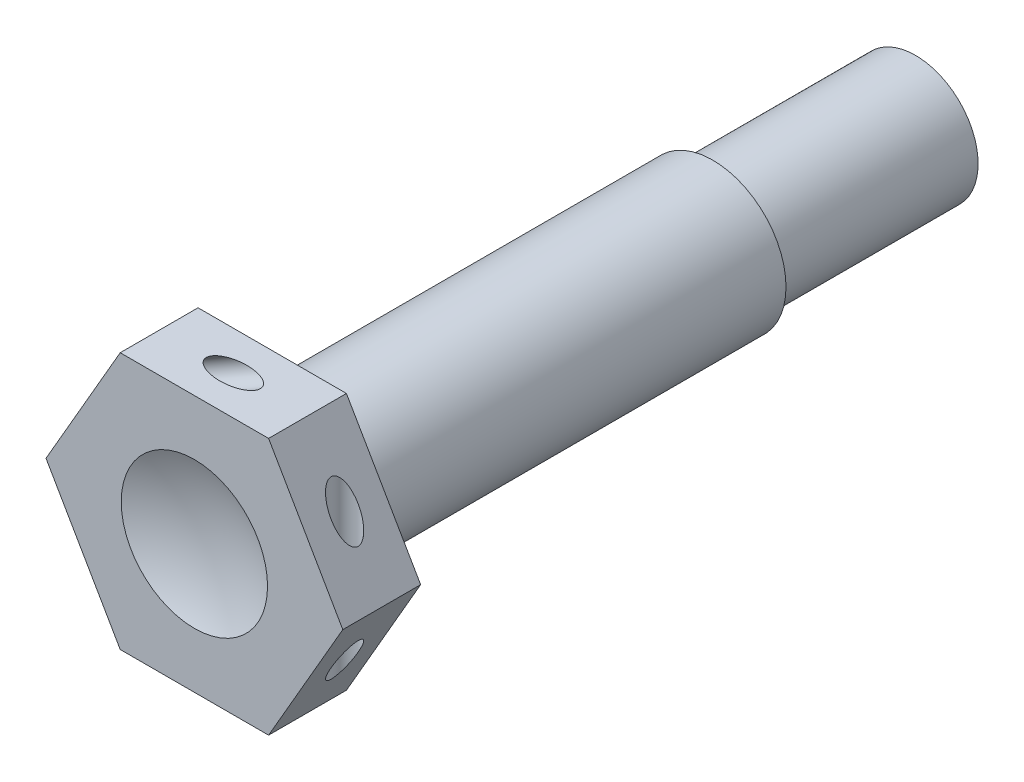
SolidWorks part; units mm, degrees
material "Alloy Steel"
ref_plane "Plane1" through (0, 0, 0) normal (0, 0, 1) x (1, 0, 0)
ref_plane "Plane2" through (0, 0, 0) normal (0, 1, 0) x (1, 0, 0)
ref_plane "Plane3" through (0, 0, 0) normal (1, 0, 0) x (0, 0, -1)
ref_axis "Axis1" through (-83.9706, 0, 0) along (1, 0, 0)
ref_axis "Axis2" through (0, 0, -29.3719) along (0, 0, 1)
ref_axis "Axis3" through (0, 6.1119, 0) along (0, -1, 0)
sketch "Sketch1" plane through (0, 0, 0) normal (0, 0, 1) x (1, 0, 0)
  line L1 (3.2079, 5.5562) -> (-3.2079, 5.5562)
  line L2 (-3.2079, 5.5562) -> (-6.4158, 0)
  line L3 (-6.4158, 0) -> (-3.2079, -5.5563)
  line L4 (-3.2079, -5.5563) -> (3.2079, -5.5563)
  line L5 (3.2079, -5.5563) -> (6.4158, 0)
  line L6 (6.4158, 0) -> (3.2079, 5.5562)
  circle A0 centre (0, 0) radius 5.5562 construction
  dimension "D1" = 11.1125
extrude "Boss-Extrude1" add sketch "Sketch1" along normal blind 3.3655
sketch "Sketch2" plane through (0, 0, 0) normal (0, 0, -1) x (-1, 0, 0)
  circle A0 centre (0, 0) radius 3.1623
  dimension "D1" = 6.3246
extrude "Boss-Extrude2" add sketch "Sketch2" along normal blind 19.05
sketch "Sketch3" plane through (0, 0, -19.05) normal (0, 0, -1) x (-1, 0, 0)
  circle A0 centre (0, 0) radius 2.7051
  dimension "D1" = 5.4102
extrude "Boss-Extrude3" add sketch "Sketch3" along normal blind 8.763
sketch "Sketch4" plane through (0, 0, 0) normal (1, 0, 0) x (0, 0, -1)
  line L0 (-3.3655, 0) -> (-3.3655, 3.1623)
  line L1 (-3.3655, 0) -> (-3.3655, 5.5562) construction
  line L2 (-3.3655, 0) -> (0, 0) construction
  line L3 (-3.3655, 0) -> (-2.6644, 0)
  line L4 (-2.6644, 0) -> (-2.6644, 2.4426) construction
  line L5 (-3.3655, 3.1623) -> (-3.5111, 3.4745) construction
  arc A0 (-3.3655, 3.1623) -> (-2.6644, 0) centre (-10.1471, 0) cw
  dimension "D1" = 3.1623
  dimension "D2" = 25
revolve "Cut-Revolve1" cut sketch "Sketch4" angle 360 about L3
sketch "Sketch5" plane through (0, 0, 0) normal (0, 1, 0) x (1, 0, 0)
  line L0 (4.8119, -1.6827) -> (6.4158, -1.6827) construction
  line L1 (6.4158, -3.3655) -> (6.4158, 0) construction
  line L2 (4.8119, -1.6827) -> (3.2079, -1.6827) construction
  line L4 (3.2079, -3.3655) -> (3.2079, 0) construction
  circle A0 centre (4.8119, -1.6827) radius 0.5842
  dimension "D1" = 1.1684
extrude "Cut-Extrude1" cut sketch "Sketch5" against normal through all and the other way through all
pattern_circular "CirPattern1" count 3 over 360 about axis through (0, 0, -29.3719) along (0, 0, 1) of "Cut-Extrude1"
equation "\"hexwid\"= 0.4375"
equation "\"hexht\"= 0.1325"
equation "\"gripd\"= 0.249"
equation "\"threadd\"= 0.213"
equation "\"threadlen\"= 0.37"
equation "\"wd\"= 0.046"
equation "\"griplen\"= 0.75"
equation "\"D1@Sketch1\" = \"hexwid\""
equation "\"D1@Boss-Extrude1\" = \"hexht\""
equation "\"D1@Sketch2\" = \"gripd\""
equation "\"D1@Boss-Extrude2\" = \"griplen\""
equation "\"D1@Sketch3\" = \"threadd\""
equation "\"D1@Sketch4\" = \"gripd\"/2"
equation "\"D2@Sketch4\" = 25deg"
equation "\"D1@Cut-Revolve1\" = 360deg"
equation "\"D1@Sketch5\" = \"wd\""
equation "\"D3@CirPattern1\" = 360deg"
equation "\"D1@CirPattern1\" = 3"
